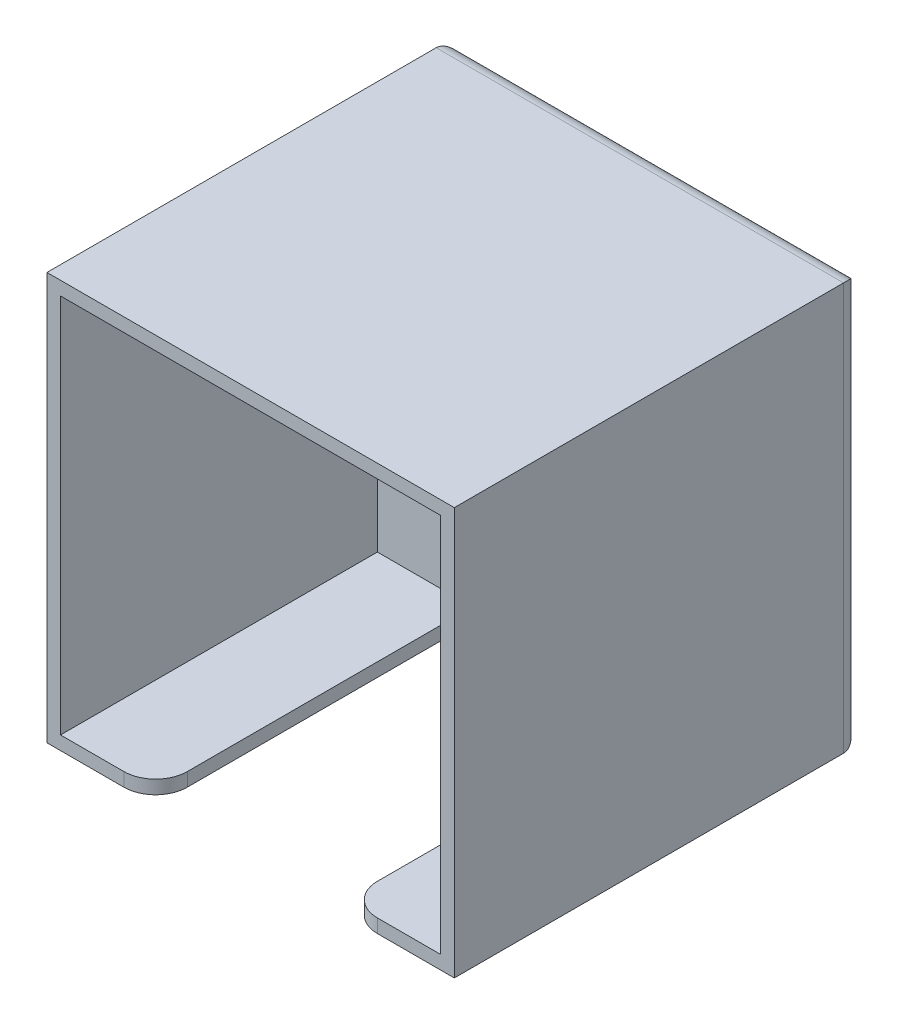
SolidWorks part; units mm, degrees
ref_plane "前视基准面" through (0, 0, 0) normal (0, 0, 1) x (1, 0, 0)
ref_plane "上视基准面" through (0, 0, 0) normal (0, 1, 0) x (1, 0, 0)
ref_plane "右视基准面" through (0, 0, 0) normal (1, 0, 0) x (0, 0, -1)
other "Configuration Table"
sketch "草图2" plane through (0, 0, 0) normal (0, 0, 1) x (1, 0, 0)
  line L1 (-22.5, -22.5) -> (22.5, -22.5)
  line L2 (-22.5, -22.5) -> (-22.5, 22.5)
  line L3 (-22.5, 22.5) -> (22.5, 22.5)
  line L4 (22.5, -22.5) -> (22.5, 22.5)
  line L5 (-22.5, -22.5) -> (22.5, 22.5) construction
  line L6 (-22.5, 22.5) -> (22.5, -22.5) construction
  point P0 (0, 0)
  dimension "D1" = 45
extrude "凸台-拉伸1" add sketch "草图2" along normal blind 45
sketch "草图3" plane through (0, 0, 45) normal (0, 0, 1) x (1, 0, 0)
  line L2 (-21, -21) -> (21, -21)
  line L3 (-21, -21) -> (-21, 21)
  line L4 (-21, 21) -> (21, 21)
  line L5 (21, -21) -> (21, 21)
  line L6 (-21, -21) -> (21, 21) construction
  line L7 (-21, 21) -> (21, -21) construction
  point P2 (0, 0)
  dimension "D1" = 42
extrude "切除-拉伸1" cut sketch "草图3" against normal blind 35
sketch "草图4" plane through (0, -22.5, 0) normal (0, -1, 0) x (1, 0, 0)
  line L0 (-22.5, 45) -> (22.5, 45) construction
  line L1 (-10.5, 10) -> (10.5, 10)
  line L2 (-10.5, 10) -> (-10.5, 45)
  line L3 (-10.5, 45) -> (10.5, 45)
  line L4 (10.5, 10) -> (10.5, 45)
  line L5 (-10.5, 10) -> (10.5, 45) construction
  line L6 (-10.5, 45) -> (10.5, 10) construction
  line L7 (-22.5, 0) -> (22.5, 0) construction
  line L8 (0, 0) -> (0, 45) construction
  line L9 (22.5, 45) -> (22.5, 0) construction
  point P0 (0, 27.5)
  point P9 (0, 0)
  dimension "D1" = 10
  dimension "D2" = 12
extrude "切除-拉伸2" cut sketch "草图4" against normal up to next
fillet "圆角2" radius 3.5 2 edges at (-10.5, -21.75, 45) (10.5, -21.75, 45)
fillet "圆角3" radius 2 4 edges at (0, -22.5, 0) (-22.5, 0, 0) (0, 22.5, 0) (22.5, 0, 0)
